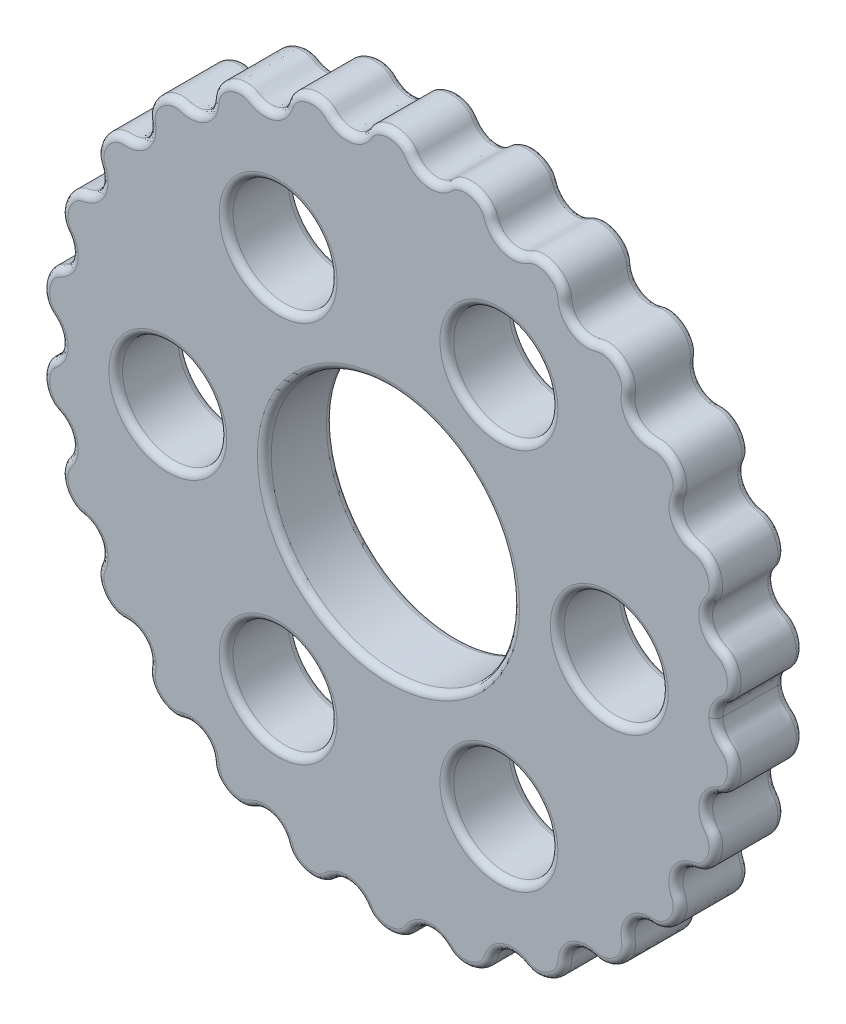
SolidWorks part; units mm, degrees
ref_plane "Front Plane" through (0, 0, 0) normal (0, 0, 1) x (1, 0, 0)
ref_plane "Top Plane" through (0, 0, 0) normal (0, 1, 0) x (1, 0, 0)
ref_plane "Right Plane" through (0, 0, 0) normal (1, 0, 0) x (0, 0, -1)
sketch "Sketch2" plane through (0, 0, 5.6053) normal (0, 0, 1) x (1, 0, 0)
  line L0 (0, 0) -> (16, 0) construction
  circle A1 centre (0, 0) radius 9.0043
  circle A2 centre (8, 13.8564) radius 3.775
  circle A3 centre (16, 0) radius 3.775
  circle A4 centre (8, -13.8564) radius 3.775
  circle A5 centre (-8, -13.8564) radius 3.775
  circle A6 centre (-16, 0) radius 3.775
  circle A7 centre (-8, 13.8564) radius 3.775
  spline S0 degree 4 poles (23.0037, 5.8458) (23.0203, 5.7223) (23.0794, 5.4789) (23.2221, 5.1817) (23.4626, 4.9066) (23.6795, 4.7368) (23.8391, 4.6378) (23.9718, 4.5676) (24.1072, 4.503) (24.2388, 4.4304) (24.4054, 4.3116) (24.5912, 4.1306) (24.7754, 3.876) (24.9327, 3.5431) (25.0483, 3.1257) (25.0761, 2.7055) (25.0224, 2.3013) (24.8965, 1.9437) (24.7582, 1.6923) (24.6064, 1.5045) (24.4596, 1.3769) (24.3107, 1.2527) (24.1813, 1.13) (24.0543, 0.9823) (23.938, 0.8063) (23.8505, 0.6319) (23.7934, 0.4738) (23.7588, 0.3351) (23.7414, 0.2342) (23.7333, 0.1668) (23.7277, 0.0957) (23.725, 0.0326) (23.7245, -0.0144) (23.7273, -0.0932) (23.7343, -0.1857) (23.7483, -0.2803) (23.7722, -0.3912) (23.8037, -0.4996) (23.8526, -0.6319) (23.9324, -0.7986) (24.0371, -0.9605) (24.1664, -1.1132) (24.2951, -1.2379) (24.4038, -1.3312) (24.514, -1.4227) (24.6167, -1.5229) (24.7397, -1.6722) (24.8666, -1.8806) (24.9775, -2.1535) (25.05, -2.49) (25.0678, -2.8386) (25.0298, -3.1905) (24.9348, -3.5366) (24.7807, -3.8663) (24.6006, -4.119) (24.4193, -4.2992) (24.2573, -4.4184) (24.1298, -4.4917) (23.9974, -4.5553) (23.8668, -4.6224) (23.709, -4.7166) (23.4971, -4.8753) (23.2602, -5.13) (23.06, -5.5023) (22.9668, -5.9508) (22.998, -6.362) (23.0998, -6.6748) (23.2181, -6.9001) (23.3176, -7.0522) (23.4035, -7.1692) (23.488, -7.2875) (23.56, -7.4139) (23.6371, -7.5903) (23.7025, -7.8212) (23.7475, -8.1895) (23.7046, -8.6153) (23.5731, -9.0303) (23.3553, -9.414) (23.1236, -9.6966) (22.8856, -9.8973) (22.6643, -10.0268) (22.4772, -10.1012) (22.3354, -10.14) (22.1917, -10.1697) (22.0491, -10.2047) (21.874, -10.26) (21.6255, -10.3685) (21.3269, -10.5711) (21.0437, -10.9023) (20.8569, -11.3338) (20.8056, -11.7447) (20.841, -12.0653) (20.9071, -12.3034) (20.9676, -12.4656) (21.021, -12.5933) (21.0822, -12.7553) (21.1313, -12.9726) (21.1455, -13.2444) (21.0948, -13.6461) (20.9479, -14.051) (20.716, -14.4248) (20.4051, -14.7469) (20.103, -14.9665) (19.8146, -15.1019) (19.5606, -15.1696) (19.3547, -15.1903) (19.2221, -15.1888) (19.1086, -15.1855) (18.995, -15.1853) (18.8815, -15.1895) (18.7118, -15.2065) (18.4439, -15.2645) (18.1117, -15.4058) (17.7742, -15.6727) (17.5121, -16.0483) (17.3806, -16.4277) (17.3468, -16.7368) (17.3574, -16.9752) (17.3781, -17.1416) (17.3988, -17.2742) (17.4171, -17.4411) (17.4116, -17.6602) (17.3598, -17.9256) (17.2132, -18.3039) (16.9296, -18.7242) (16.5497, -19.061) (16.1013, -19.2909) (15.7127, -19.392) (15.4438, -19.4132) (15.2236, -19.3942) (15.0228, -19.3476) (14.8253, -19.2892) (14.5504, -19.237) (14.1962, -19.2348) (13.7976, -19.3265) (13.3929, -19.5509) (13.0927, -19.8602) (12.9191, -20.1735) (12.8336, -20.4318) (12.7947, -20.6157) (12.7743, -20.7647) (12.7615, -20.9144) (12.7433, -21.0637) (12.6954, -21.2634) (12.5957, -21.5045) (12.4256, -21.7711) (12.1716, -22.0409) (11.8129, -22.3094) (11.4108, -22.4937) (10.9862, -22.5887) (10.6101, -22.5864) (10.3721, -22.5473) (10.1892, -22.4907) (10.0584, -22.4347) (9.9338, -22.3664) (9.81, -22.2969) (9.6507, -22.2183) (9.4189, -22.1297) (9.1053, -22.0658) (8.7004, -22.0785) (8.2681, -22.2156) (7.9185, -22.4522) (7.6878, -22.7163) (7.5514, -22.9457) (7.4743, -23.1141) (7.4217, -23.2525) (7.3745, -23.3928) (7.3187, -23.5301) (7.2216, -23.708) (7.0655, -23.913) (6.8362, -24.1258) (6.5262, -24.3219) (6.1144, -24.4927) (5.6801, -24.5722) (5.2446, -24.5597) (4.8794, -24.4637) (4.6581, -24.366) (4.4951, -24.2648) (4.3828, -24.1775) (4.2789, -24.0806) (4.1747, -23.9841) (4.0379, -23.8707) (3.8273, -23.7279) (3.5241, -23.5902) (3.1183, -23.5153) (2.6658, -23.5604) (2.2792, -23.7158) (2.0049, -23.916) (1.8238, -24.1052) (1.71, -24.2525) (1.6267, -24.3758) (1.5466, -24.5011) (1.4565, -24.6199) (1.3207, -24.7622) (1.1279, -24.9136) (0.8712, -25.0555) (0.5491, -25.1669) (0.1207, -25.2418) (-0.3205, -25.2256) (-0.7535, -25.1153) (-1.1028, -24.9304) (-1.3027, -24.7782) (-1.4408, -24.6375) (-1.53, -24.5249) (-1.6084, -24.4048) (-1.6871, -24.2851) (-1.794, -24.141) (-1.9709, -23.9454) (-2.248, -23.731) (-2.6436, -23.5634) (-3.111, -23.5139) (-3.5241, -23.5902) (-3.8273, -23.7279) (-4.0379, -23.8707) (-4.1747, -23.9841) (-4.2789, -24.0806) (-4.3828, -24.1775) (-4.4951, -24.2648) (-4.6581, -24.366) (-4.8794, -24.4637) (-5.2446, -24.5597) (-5.6801, -24.5722) (-6.1144, -24.4927) (-6.5262, -24.3219) (-6.8362, -24.1258) (-7.0655, -23.913) (-7.2216, -23.708) (-7.3187, -23.5301) (-7.3745, -23.3928) (-7.4217, -23.2525) (-7.4743, -23.1141) (-7.5514, -22.9457) (-7.6878, -22.7163) (-7.9185, -22.4522) (-8.2681, -22.2156) (-8.7004, -22.0785) (-9.1053, -22.0658) (-9.4189, -22.1297) (-9.6507, -22.2183) (-9.81, -22.2969) (-9.9338, -22.3664) (-10.0584, -22.4347) (-10.1892, -22.4907) (-10.3721, -22.5473) (-10.6101, -22.5864) (-10.9862, -22.5887) (-11.4108, -22.4937) (-11.8129, -22.3094) (-12.1716, -22.0409) (-12.4256, -21.7711) (-12.5957, -21.5045) (-12.6954, -21.2634) (-12.7433, -21.0637) (-12.7615, -20.9144) (-12.7743, -20.7647) (-12.7947, -20.6157) (-12.8336, -20.4318) (-12.9191, -20.1735) (-13.0927, -19.8602) (-13.3929, -19.5509) (-13.7976, -19.3265) (-14.1962, -19.2348) (-14.5504, -19.237) (-14.8253, -19.2892) (-15.0228, -19.3476) (-15.2236, -19.3942) (-15.4438, -19.4132) (-15.7127, -19.392) (-16.1013, -19.2909) (-16.5497, -19.061) (-16.9296, -18.7242) (-17.2132, -18.3039) (-17.3598, -17.9256) (-17.4116, -17.6602) (-17.4171, -17.4411) (-17.3988, -17.2742) (-17.3781, -17.1416) (-17.3574, -16.9752) (-17.3468, -16.7368) (-17.3806, -16.4277) (-17.5121, -16.0483) (-17.7742, -15.6727) (-18.1117, -15.4058) (-18.4439, -15.2645) (-18.7118, -15.2065) (-18.8815, -15.1895) (-18.995, -15.1853) (-19.1086, -15.1855) (-19.2221, -15.1888) (-19.3547, -15.1903) (-19.5606, -15.1696) (-19.8146, -15.1019) (-20.103, -14.9665) (-20.4051, -14.7469) (-20.716, -14.4248) (-20.9479, -14.051) (-21.0948, -13.6461) (-21.1455, -13.2444) (-21.1313, -12.9726) (-21.0822, -12.7553) (-21.021, -12.5933) (-20.9676, -12.4656) (-20.9071, -12.3034) (-20.841, -12.0653) (-20.8056, -11.7447) (-20.8569, -11.3338) (-21.0437, -10.9023) (-21.3269, -10.5711) (-21.6255, -10.3685) (-21.874, -10.26) (-22.0491, -10.2047) (-22.1917, -10.1697) (-22.3354, -10.14) (-22.4772, -10.1012) (-22.6643, -10.0268) (-22.8856, -9.8973) (-23.1236, -9.6966) (-23.3553, -9.414) (-23.5731, -9.0303) (-23.7046, -8.6153) (-23.7475, -8.1895) (-23.7025, -7.8212) (-23.6371, -7.5903) (-23.56, -7.4139) (-23.488, -7.2875) (-23.4035, -7.1692) (-23.3176, -7.0522) (-23.2181, -6.9001) (-23.0998, -6.6748) (-22.998, -6.362) (-22.9668, -5.9508) (-23.06, -5.5023) (-23.2602, -5.13) (-23.4971, -4.8753) (-23.709, -4.7166) (-23.8668, -4.6224) (-23.9974, -4.5553) (-24.1298, -4.4917) (-24.2573, -4.4184) (-24.4193, -4.2992) (-24.6006, -4.119) (-24.7807, -3.8663) (-24.9348, -3.5366) (-25.0298, -3.1905) (-25.0678, -2.8386) (-25.05, -2.49) (-24.9775, -2.1535) (-24.8666, -1.8806) (-24.7397, -1.6722) (-24.6167, -1.5229) (-24.514, -1.4227) (-24.4038, -1.3312) (-24.2951, -1.2379) (-24.1664, -1.1132) (-24.0371, -0.9605) (-23.9324, -0.7986) (-23.8526, -0.6319) (-23.8037, -0.4996) (-23.7722, -0.3912) (-23.7483, -0.2803) (-23.7343, -0.1857) (-23.7273, -0.0932) (-23.7245, -0.0144) (-23.725, 0.0326) (-23.7277, 0.0957) (-23.7333, 0.1668) (-23.7414, 0.2342) (-23.7588, 0.3351) (-23.7934, 0.4738) (-23.8505, 0.6319) (-23.938, 0.8063) (-24.0543, 0.9823) (-24.1813, 1.13) (-24.3107, 1.2527) (-24.4596, 1.3769) (-24.6064, 1.5045) (-24.7582, 1.6923) (-24.8965, 1.9437) (-25.0224, 2.3014) (-25.0767, 2.7104) (-25.047, 3.1407) (-24.9235, 3.5716) (-24.7509, 3.9196) (-24.5491, 4.1808) (-24.3464, 4.3608) (-24.1669, 4.4726) (-24.0469, 4.5314) (-23.9443, 4.5823) (-23.8099, 4.6547) (-23.6481, 4.7565) (-23.428, 4.9381) (-23.1927, 5.2368) (-23.0695, 5.5154) (-23.0186, 5.7347) (-23.0037, 5.8458) knots 0 0 0 0 0 0.004792 0.009584 0.01247 0.013912 0.015355 0.016798 0.018241 0.019684 0.021127 0.024649 0.02817 0.031692 0.035214 0.041226 0.044232 0.047238 0.049726 0.052214 0.053458 0.054702 0.057189 0.059059 0.060929 0.062799 0.064669 0.065525 0.066381 0.066809 0.067237 0.068093 0.068635 0.069177 0.070262 0.071346 0.072431 0.073516 0.0746 0.076769 0.079523 0.080901 0.082278 0.083655 0.085032 0.086409 0.087786 0.091081 0.094376 0.097671 0.100966 0.104448 0.10793 0.111412 0.114894 0.116306 0.117718 0.119129 0.120541 0.121953 0.123365 0.126188 0.130698 0.135209 0.139389 0.143569 0.146362 0.147758 0.149154 0.150551 0.151947 0.153343 0.154739 0.15794 0.16114 0.167541 0.171036 0.174532 0.178027 0.181523 0.182934 0.184345 0.185756 0.187168 0.188579 0.18999 0.192812 0.197567 0.202321 0.20648 0.21064 0.213301 0.214632 0.215963 0.217294 0.218625 0.221287 0.224494 0.227701 0.234115 0.237687 0.241259 0.244831 0.248403 0.249859 0.251314 0.25277 0.253498 0.254226 0.255682 0.257137 0.260049 0.264737 0.269426 0.273427 0.277429 0.280009 0.281299 0.282589 0.283879 0.285169 0.287749 0.290984 0.294219 0.30069 0.307051 0.310231 0.313411 0.316051 0.317371 0.318692 0.321332 0.323972 0.328095 0.332218 0.336872 0.341526 0.344415 0.34586 0.347305 0.348749 0.350194 0.351639 0.353084 0.356629 0.360174 0.363719 0.367265 0.373774 0.377029 0.380283 0.381649 0.383014 0.384379 0.385745 0.38711 0.388475 0.391206 0.395267 0.399327 0.403873 0.408418 0.411264 0.412687 0.41411 0.415533 0.416956 0.418379 0.419802 0.423312 0.426821 0.43033 0.433839 0.440376 0.443644 0.446913 0.448278 0.449644 0.451009 0.452374 0.45374 0.455105 0.457836 0.462139 0.466442 0.470768 0.475094 0.477954 0.479385 0.480815 0.482245 0.483675 0.485106 0.486536 0.489798 0.493061 0.496324 0.499586 0.506451 0.509883 0.513315 0.514694 0.516072 0.51745 0.518829 0.520207 0.521585 0.524342 0.52895 0.533558 0.537861 0.542164 0.544895 0.54626 0.547626 0.548991 0.550356 0.551722 0.553087 0.556356 0.559624 0.566161 0.56967 0.573179 0.576689 0.580198 0.581621 0.583044 0.584467 0.58589 0.587313 0.588736 0.591582 0.596127 0.600673 0.604734 0.608794 0.611525 0.61289 0.614256 0.615621 0.616986 0.618351 0.619717 0.622971 0.626226 0.632735 0.636281 0.639826 0.643371 0.646916 0.648361 0.649806 0.651251 0.652695 0.65414 0.655585 0.658475 0.663128 0.667782 0.671905 0.676028 0.678668 0.681309 0.682629 0.683949 0.686589 0.689769 0.692949 0.69931 0.705781 0.709016 0.712252 0.714831 0.716121 0.717411 0.718701 0.719991 0.722571 0.726573 0.730574 0.735263 0.739951 0.742863 0.744318 0.745774 0.746502 0.74723 0.748686 0.750142 0.751597 0.755169 0.758741 0.762313 0.765885 0.772299 0.775506 0.778713 0.781375 0.782706 0.784037 0.785368 0.786699 0.78936 0.79352 0.797679 0.802433 0.807188 0.81001 0.811421 0.812832 0.814244 0.815655 0.817066 0.818477 0.821973 0.825468 0.828964 0.832459 0.83886 0.84206 0.845261 0.846657 0.848053 0.84945 0.850846 0.852242 0.853638 0.856431 0.860611 0.864792 0.869302 0.873812 0.876635 0.878047 0.879459 0.880871 0.882282 0.883694 0.885106 0.888588 0.89207 0.895552 0.899034 0.902329 0.905624 0.908919 0.912214 0.913591 0.914968 0.916345 0.917722 0.919099 0.920477 0.923231 0.9254 0.926485 0.927569 0.928654 0.929738 0.930823 0.931365 0.931907 0.932763 0.933191 0.933619 0.934475 0.935331 0.937201 0.939071 0.940941 0.942811 0.945298 0.946542 0.947786 0.950274 0.952762 0.955768 0.958774 0.964786 0.968499 0.972211 0.975924 0.979636 0.981104 0.982571 0.984039 0.984773 0.985507 0.988442 0.991378 0.995689 1 1 1 1 1 construction
  spline S1 degree 4 poles (23.725, 0) (23.725, -0.0122) (23.7253, -0.0367) (23.7273, -0.0932) (23.7343, -0.1857) (23.7483, -0.2803) (23.7722, -0.3912) (23.8037, -0.4996) (23.8526, -0.6319) (23.9324, -0.7986) (24.0371, -0.9605) (24.1664, -1.1132) (24.2951, -1.2379) (24.4038, -1.3312) (24.514, -1.4227) (24.6167, -1.5229) (24.7397, -1.6722) (24.8666, -1.8806) (24.9775, -2.1535) (25.05, -2.49) (25.0678, -2.8386) (25.0298, -3.1905) (24.9348, -3.5366) (24.7807, -3.8663) (24.6006, -4.119) (24.4193, -4.2992) (24.2573, -4.4184) (24.1298, -4.4917) (23.9974, -4.5553) (23.8668, -4.6224) (23.709, -4.7166) (23.4971, -4.8753) (23.2602, -5.13) (23.06, -5.5023) (22.9668, -5.9508) (22.998, -6.362) (23.0998, -6.6748) (23.2181, -6.9001) (23.3176, -7.0522) (23.4035, -7.1692) (23.488, -7.2875) (23.56, -7.4139) (23.6371, -7.5903) (23.7025, -7.8212) (23.7475, -8.1895) (23.7046, -8.6153) (23.5731, -9.0303) (23.3553, -9.414) (23.1236, -9.6966) (22.8856, -9.8973) (22.6643, -10.0268) (22.4772, -10.1012) (22.3354, -10.14) (22.1917, -10.1697) (22.0491, -10.2047) (21.874, -10.26) (21.6255, -10.3685) (21.3269, -10.5711) (21.0437, -10.9023) (20.8569, -11.3338) (20.8056, -11.7447) (20.841, -12.0653) (20.9071, -12.3034) (20.9676, -12.4656) (21.021, -12.5933) (21.0822, -12.7553) (21.1313, -12.9726) (21.1455, -13.2444) (21.0948, -13.6461) (20.9479, -14.051) (20.716, -14.4248) (20.4051, -14.7469) (20.103, -14.9665) (19.8146, -15.1019) (19.5606, -15.1696) (19.3547, -15.1903) (19.2221, -15.1888) (19.1086, -15.1855) (18.995, -15.1853) (18.8815, -15.1895) (18.7118, -15.2065) (18.4439, -15.2645) (18.1117, -15.4058) (17.7742, -15.6727) (17.5121, -16.0483) (17.3806, -16.4277) (17.3468, -16.7368) (17.3574, -16.9752) (17.3781, -17.1416) (17.3988, -17.2742) (17.4171, -17.4411) (17.4116, -17.6602) (17.3598, -17.9256) (17.2132, -18.3039) (16.9296, -18.7242) (16.5497, -19.061) (16.1013, -19.2909) (15.7127, -19.392) (15.4438, -19.4132) (15.2236, -19.3942) (15.0228, -19.3476) (14.8253, -19.2892) (14.5504, -19.237) (14.1962, -19.2348) (13.7976, -19.3265) (13.3929, -19.5509) (13.0927, -19.8602) (12.9191, -20.1735) (12.8336, -20.4318) (12.7947, -20.6157) (12.7743, -20.7647) (12.7615, -20.9144) (12.7433, -21.0637) (12.6954, -21.2634) (12.5957, -21.5045) (12.4256, -21.7711) (12.1716, -22.0409) (11.8129, -22.3094) (11.4108, -22.4937) (10.9862, -22.5887) (10.6101, -22.5864) (10.3721, -22.5473) (10.1892, -22.4907) (10.0584, -22.4347) (9.9338, -22.3664) (9.81, -22.2969) (9.6507, -22.2183) (9.4189, -22.1297) (9.1053, -22.0658) (8.7004, -22.0785) (8.2681, -22.2156) (7.9185, -22.4522) (7.6878, -22.7163) (7.5514, -22.9457) (7.4743, -23.1141) (7.4217, -23.2525) (7.3745, -23.3928) (7.3187, -23.5301) (7.2216, -23.708) (7.0655, -23.913) (6.8362, -24.1258) (6.5262, -24.3219) (6.1144, -24.4927) (5.6801, -24.5722) (5.2446, -24.5597) (4.8794, -24.4637) (4.6581, -24.366) (4.4951, -24.2648) (4.3828, -24.1775) (4.2789, -24.0806) (4.1747, -23.9841) (4.0379, -23.8707) (3.8273, -23.7279) (3.5241, -23.5902) (3.1183, -23.5153) (2.6658, -23.5604) (2.2792, -23.7158) (2.0049, -23.916) (1.8238, -24.1052) (1.71, -24.2525) (1.6267, -24.3758) (1.5466, -24.5011) (1.4565, -24.6199) (1.3207, -24.7622) (1.1279, -24.9136) (0.8712, -25.0555) (0.5491, -25.1669) (0.1207, -25.2418) (-0.3205, -25.2256) (-0.7535, -25.1153) (-1.1028, -24.9304) (-1.3027, -24.7782) (-1.4408, -24.6375) (-1.53, -24.5249) (-1.6084, -24.4048) (-1.6871, -24.2851) (-1.794, -24.141) (-1.9709, -23.9454) (-2.248, -23.731) (-2.6436, -23.5634) (-3.111, -23.5139) (-3.5241, -23.5902) (-3.8273, -23.7279) (-4.0379, -23.8707) (-4.1747, -23.9841) (-4.2789, -24.0806) (-4.3828, -24.1775) (-4.4951, -24.2648) (-4.6581, -24.366) (-4.8794, -24.4637) (-5.2446, -24.5597) (-5.6801, -24.5722) (-6.1144, -24.4927) (-6.5262, -24.3219) (-6.8362, -24.1258) (-7.0655, -23.913) (-7.2216, -23.708) (-7.3187, -23.5301) (-7.3745, -23.3928) (-7.4217, -23.2525) (-7.4743, -23.1141) (-7.5514, -22.9457) (-7.6878, -22.7163) (-7.9185, -22.4522) (-8.2681, -22.2156) (-8.7004, -22.0785) (-9.1053, -22.0658) (-9.4189, -22.1297) (-9.6507, -22.2183) (-9.81, -22.2969) (-9.9338, -22.3664) (-10.0584, -22.4347) (-10.1892, -22.4907) (-10.3721, -22.5473) (-10.6101, -22.5864) (-10.9862, -22.5887) (-11.4108, -22.4937) (-11.8129, -22.3094) (-12.1716, -22.0409) (-12.4256, -21.7711) (-12.5957, -21.5045) (-12.6954, -21.2634) (-12.7433, -21.0637) (-12.7615, -20.9144) (-12.7743, -20.7647) (-12.7947, -20.6157) (-12.8336, -20.4318) (-12.9191, -20.1735) (-13.0927, -19.8602) (-13.3929, -19.5509) (-13.7976, -19.3265) (-14.1962, -19.2348) (-14.5504, -19.237) (-14.8253, -19.2892) (-15.0228, -19.3476) (-15.2236, -19.3942) (-15.4438, -19.4132) (-15.7127, -19.392) (-16.1013, -19.2909) (-16.5497, -19.061) (-16.9296, -18.7242) (-17.2132, -18.3039) (-17.3598, -17.9256) (-17.4116, -17.6602) (-17.4171, -17.4411) (-17.3988, -17.2742) (-17.3781, -17.1416) (-17.3574, -16.9752) (-17.3468, -16.7368) (-17.3806, -16.4277) (-17.5121, -16.0483) (-17.7742, -15.6727) (-18.1117, -15.4058) (-18.4439, -15.2645) (-18.7118, -15.2065) (-18.8815, -15.1895) (-18.995, -15.1853) (-19.1086, -15.1855) (-19.2221, -15.1888) (-19.3547, -15.1903) (-19.5606, -15.1696) (-19.8146, -15.1019) (-20.103, -14.9665) (-20.4051, -14.7469) (-20.716, -14.4248) (-20.9479, -14.051) (-21.0948, -13.6461) (-21.1455, -13.2444) (-21.1313, -12.9726) (-21.0822, -12.7553) (-21.021, -12.5933) (-20.9676, -12.4656) (-20.9071, -12.3034) (-20.841, -12.0653) (-20.8056, -11.7447) (-20.8569, -11.3338) (-21.0437, -10.9023) (-21.3269, -10.5711) (-21.6255, -10.3685) (-21.874, -10.26) (-22.0491, -10.2047) (-22.1917, -10.1697) (-22.3354, -10.14) (-22.4772, -10.1012) (-22.6643, -10.0268) (-22.8856, -9.8973) (-23.1236, -9.6966) (-23.3553, -9.414) (-23.5731, -9.0303) (-23.7046, -8.6153) (-23.7475, -8.1895) (-23.7025, -7.8212) (-23.6371, -7.5903) (-23.56, -7.4139) (-23.488, -7.2875) (-23.4035, -7.1692) (-23.3176, -7.0522) (-23.2181, -6.9001) (-23.0998, -6.6748) (-22.998, -6.362) (-22.9668, -5.9508) (-23.06, -5.5023) (-23.2602, -5.13) (-23.4971, -4.8753) (-23.709, -4.7166) (-23.8668, -4.6224) (-23.9974, -4.5553) (-24.1298, -4.4917) (-24.2573, -4.4184) (-24.4193, -4.2992) (-24.6006, -4.119) (-24.7807, -3.8663) (-24.9348, -3.5366) (-25.0298, -3.1905) (-25.0678, -2.8386) (-25.05, -2.49) (-24.9775, -2.1535) (-24.8666, -1.8806) (-24.7397, -1.6722) (-24.6167, -1.5229) (-24.514, -1.4227) (-24.4038, -1.3312) (-24.2951, -1.2379) (-24.1664, -1.1132) (-24.0371, -0.9605) (-23.9324, -0.7986) (-23.8526, -0.6319) (-23.8037, -0.4996) (-23.7722, -0.3912) (-23.7483, -0.2803) (-23.7343, -0.1857) (-23.7273, -0.0932) (-23.7253, -0.0367) (-23.725, -0.0122) (-23.725, 0) knots 0.068093 0.068093 0.068093 0.068093 0.068093 0.068635 0.069177 0.070262 0.071346 0.072431 0.073516 0.0746 0.076769 0.079523 0.080901 0.082278 0.083655 0.085032 0.086409 0.087786 0.091081 0.094376 0.097671 0.100966 0.104448 0.10793 0.111412 0.114894 0.116306 0.117718 0.119129 0.120541 0.121953 0.123365 0.126188 0.130698 0.135209 0.139389 0.143569 0.146362 0.147758 0.149154 0.150551 0.151947 0.153343 0.154739 0.15794 0.16114 0.167541 0.171036 0.174532 0.178027 0.181523 0.182934 0.184345 0.185756 0.187168 0.188579 0.18999 0.192812 0.197567 0.202321 0.20648 0.21064 0.213301 0.214632 0.215963 0.217294 0.218625 0.221287 0.224494 0.227701 0.234115 0.237687 0.241259 0.244831 0.248403 0.249859 0.251314 0.25277 0.253498 0.254226 0.255682 0.257137 0.260049 0.264737 0.269426 0.273427 0.277429 0.280009 0.281299 0.282589 0.283879 0.285169 0.287749 0.290984 0.294219 0.30069 0.307051 0.310231 0.313411 0.316051 0.317371 0.318692 0.321332 0.323972 0.328095 0.332218 0.336872 0.341526 0.344415 0.34586 0.347305 0.348749 0.350194 0.351639 0.353084 0.356629 0.360174 0.363719 0.367265 0.373774 0.377029 0.380283 0.381649 0.383014 0.384379 0.385745 0.38711 0.388475 0.391206 0.395267 0.399327 0.403873 0.408418 0.411264 0.412687 0.41411 0.415533 0.416956 0.418379 0.419802 0.423312 0.426821 0.43033 0.433839 0.440376 0.443644 0.446913 0.448278 0.449644 0.451009 0.452374 0.45374 0.455105 0.457836 0.462139 0.466442 0.470768 0.475094 0.477954 0.479385 0.480815 0.482245 0.483675 0.485106 0.486536 0.489798 0.493061 0.496324 0.499586 0.506451 0.509883 0.513315 0.514694 0.516072 0.51745 0.518829 0.520207 0.521585 0.524342 0.52895 0.533558 0.537861 0.542164 0.544895 0.54626 0.547626 0.548991 0.550356 0.551722 0.553087 0.556356 0.559624 0.566161 0.56967 0.573179 0.576689 0.580198 0.581621 0.583044 0.584467 0.58589 0.587313 0.588736 0.591582 0.596127 0.600673 0.604734 0.608794 0.611525 0.61289 0.614256 0.615621 0.616986 0.618351 0.619717 0.622971 0.626226 0.632735 0.636281 0.639826 0.643371 0.646916 0.648361 0.649806 0.651251 0.652695 0.65414 0.655585 0.658475 0.663128 0.667782 0.671905 0.676028 0.678668 0.681309 0.682629 0.683949 0.686589 0.689769 0.692949 0.69931 0.705781 0.709016 0.712252 0.714831 0.716121 0.717411 0.718701 0.719991 0.722571 0.726573 0.730574 0.735263 0.739951 0.742863 0.744318 0.745774 0.746502 0.74723 0.748686 0.750142 0.751597 0.755169 0.758741 0.762313 0.765885 0.772299 0.775506 0.778713 0.781375 0.782706 0.784037 0.785368 0.786699 0.78936 0.79352 0.797679 0.802433 0.807188 0.81001 0.811421 0.812832 0.814244 0.815655 0.817066 0.818477 0.821973 0.825468 0.828964 0.832459 0.83886 0.84206 0.845261 0.846657 0.848053 0.84945 0.850846 0.852242 0.853638 0.856431 0.860611 0.864792 0.869302 0.873812 0.876635 0.878047 0.879459 0.880871 0.882282 0.883694 0.885106 0.888588 0.89207 0.895552 0.899034 0.902329 0.905624 0.908919 0.912214 0.913591 0.914968 0.916345 0.917722 0.919099 0.920477 0.923231 0.9254 0.926485 0.927569 0.928654 0.929738 0.930823 0.931365 0.931907 0.931907 0.931907 0.931907 0.931907
  spline S2 degree 4 poles (23.725, 0) (23.725, 0.0122) (23.7253, 0.0367) (23.7273, 0.0932) (23.7343, 0.1857) (23.7483, 0.2803) (23.7722, 0.3912) (23.8037, 0.4996) (23.8526, 0.6319) (23.9324, 0.7986) (24.0371, 0.9605) (24.1664, 1.1132) (24.2951, 1.2379) (24.4038, 1.3312) (24.514, 1.4227) (24.6167, 1.5229) (24.7397, 1.6722) (24.8666, 1.8806) (24.9775, 2.1535) (25.05, 2.49) (25.0678, 2.8386) (25.0298, 3.1905) (24.9348, 3.5366) (24.7807, 3.8663) (24.6006, 4.119) (24.4193, 4.2992) (24.2573, 4.4184) (24.1298, 4.4917) (23.9974, 4.5553) (23.8668, 4.6224) (23.709, 4.7166) (23.4971, 4.8753) (23.2602, 5.13) (23.06, 5.5023) (22.9668, 5.9508) (22.998, 6.362) (23.0998, 6.6748) (23.2181, 6.9001) (23.3176, 7.0522) (23.4035, 7.1692) (23.488, 7.2875) (23.56, 7.4139) (23.6371, 7.5903) (23.7025, 7.8212) (23.7475, 8.1895) (23.7046, 8.6153) (23.5731, 9.0303) (23.3553, 9.414) (23.1236, 9.6966) (22.8856, 9.8973) (22.6643, 10.0268) (22.4772, 10.1012) (22.3354, 10.14) (22.1917, 10.1697) (22.0491, 10.2047) (21.874, 10.26) (21.6255, 10.3685) (21.3269, 10.5711) (21.0437, 10.9023) (20.8569, 11.3338) (20.8056, 11.7447) (20.841, 12.0653) (20.9071, 12.3034) (20.9676, 12.4656) (21.021, 12.5933) (21.0822, 12.7553) (21.1313, 12.9726) (21.1455, 13.2444) (21.0948, 13.6461) (20.9479, 14.051) (20.716, 14.4248) (20.4051, 14.7469) (20.103, 14.9665) (19.8146, 15.1019) (19.5606, 15.1696) (19.3547, 15.1903) (19.2221, 15.1888) (19.1086, 15.1855) (18.995, 15.1853) (18.8815, 15.1895) (18.7118, 15.2065) (18.4439, 15.2645) (18.1117, 15.4058) (17.7742, 15.6727) (17.5121, 16.0483) (17.3806, 16.4277) (17.3468, 16.7368) (17.3574, 16.9752) (17.3781, 17.1416) (17.3988, 17.2742) (17.4171, 17.4411) (17.4116, 17.6602) (17.3598, 17.9256) (17.2132, 18.3039) (16.9296, 18.7242) (16.5497, 19.061) (16.1013, 19.2909) (15.7127, 19.392) (15.4438, 19.4132) (15.2236, 19.3942) (15.0228, 19.3476) (14.8253, 19.2892) (14.5504, 19.237) (14.1962, 19.2348) (13.7976, 19.3265) (13.3929, 19.5509) (13.0927, 19.8602) (12.9191, 20.1735) (12.8336, 20.4318) (12.7947, 20.6157) (12.7743, 20.7647) (12.7615, 20.9144) (12.7433, 21.0637) (12.6954, 21.2634) (12.5957, 21.5045) (12.4256, 21.7711) (12.1716, 22.0409) (11.8129, 22.3094) (11.4108, 22.4937) (10.9862, 22.5887) (10.6101, 22.5864) (10.3721, 22.5473) (10.1892, 22.4907) (10.0584, 22.4347) (9.9338, 22.3664) (9.81, 22.2969) (9.6507, 22.2183) (9.4189, 22.1297) (9.1053, 22.0658) (8.7004, 22.0785) (8.2681, 22.2156) (7.9185, 22.4522) (7.6878, 22.7163) (7.5514, 22.9457) (7.4743, 23.1141) (7.4217, 23.2525) (7.3745, 23.3928) (7.3187, 23.5301) (7.2216, 23.708) (7.0655, 23.913) (6.8362, 24.1258) (6.5262, 24.3219) (6.1144, 24.4927) (5.6801, 24.5722) (5.2446, 24.5597) (4.8794, 24.4637) (4.6581, 24.366) (4.4951, 24.2648) (4.3828, 24.1775) (4.2789, 24.0806) (4.1747, 23.9841) (4.0379, 23.8707) (3.8273, 23.7279) (3.5241, 23.5902) (3.1183, 23.5153) (2.6658, 23.5604) (2.2792, 23.7158) (2.0049, 23.916) (1.8238, 24.1052) (1.71, 24.2525) (1.6267, 24.3758) (1.5466, 24.5011) (1.4565, 24.6199) (1.3207, 24.7622) (1.1279, 24.9136) (0.8712, 25.0555) (0.5491, 25.1669) (0.1207, 25.2418) (-0.3205, 25.2256) (-0.7535, 25.1153) (-1.1028, 24.9304) (-1.3027, 24.7782) (-1.4408, 24.6375) (-1.53, 24.5249) (-1.6084, 24.4048) (-1.6871, 24.2851) (-1.794, 24.141) (-1.9709, 23.9454) (-2.248, 23.731) (-2.6436, 23.5634) (-3.111, 23.5139) (-3.5241, 23.5902) (-3.8273, 23.7279) (-4.0379, 23.8707) (-4.1747, 23.9841) (-4.2789, 24.0806) (-4.3828, 24.1775) (-4.4951, 24.2648) (-4.6581, 24.366) (-4.8794, 24.4637) (-5.2446, 24.5597) (-5.6801, 24.5722) (-6.1144, 24.4927) (-6.5262, 24.3219) (-6.8362, 24.1258) (-7.0655, 23.913) (-7.2216, 23.708) (-7.3187, 23.5301) (-7.3745, 23.3928) (-7.4217, 23.2525) (-7.4743, 23.1141) (-7.5514, 22.9457) (-7.6878, 22.7163) (-7.9185, 22.4522) (-8.2681, 22.2156) (-8.7004, 22.0785) (-9.1053, 22.0658) (-9.4189, 22.1297) (-9.6507, 22.2183) (-9.81, 22.2969) (-9.9338, 22.3664) (-10.0584, 22.4347) (-10.1892, 22.4907) (-10.3721, 22.5473) (-10.6101, 22.5864) (-10.9862, 22.5887) (-11.4108, 22.4937) (-11.8129, 22.3094) (-12.1716, 22.0409) (-12.4256, 21.7711) (-12.5957, 21.5045) (-12.6954, 21.2634) (-12.7433, 21.0637) (-12.7615, 20.9144) (-12.7743, 20.7647) (-12.7947, 20.6157) (-12.8336, 20.4318) (-12.9191, 20.1735) (-13.0927, 19.8602) (-13.3929, 19.5509) (-13.7976, 19.3265) (-14.1962, 19.2348) (-14.5504, 19.237) (-14.8253, 19.2892) (-15.0228, 19.3476) (-15.2236, 19.3942) (-15.4438, 19.4132) (-15.7127, 19.392) (-16.1013, 19.2909) (-16.5497, 19.061) (-16.9296, 18.7242) (-17.2132, 18.3039) (-17.3598, 17.9256) (-17.4116, 17.6602) (-17.4171, 17.4411) (-17.3988, 17.2742) (-17.3781, 17.1416) (-17.3574, 16.9752) (-17.3468, 16.7368) (-17.3806, 16.4277) (-17.5121, 16.0483) (-17.7742, 15.6727) (-18.1117, 15.4058) (-18.4439, 15.2645) (-18.7118, 15.2065) (-18.8815, 15.1895) (-18.995, 15.1853) (-19.1086, 15.1855) (-19.2221, 15.1888) (-19.3547, 15.1903) (-19.5606, 15.1696) (-19.8146, 15.1019) (-20.103, 14.9665) (-20.4051, 14.7469) (-20.716, 14.4248) (-20.9479, 14.051) (-21.0948, 13.6461) (-21.1455, 13.2444) (-21.1313, 12.9726) (-21.0822, 12.7553) (-21.021, 12.5933) (-20.9676, 12.4656) (-20.9071, 12.3034) (-20.841, 12.0653) (-20.8056, 11.7447) (-20.8569, 11.3338) (-21.0437, 10.9023) (-21.3269, 10.5711) (-21.6255, 10.3685) (-21.874, 10.26) (-22.0491, 10.2047) (-22.1917, 10.1697) (-22.3354, 10.14) (-22.4772, 10.1012) (-22.6643, 10.0268) (-22.8856, 9.8973) (-23.1236, 9.6966) (-23.3553, 9.414) (-23.5731, 9.0303) (-23.7046, 8.6153) (-23.7475, 8.1895) (-23.7025, 7.8212) (-23.6371, 7.5903) (-23.56, 7.4139) (-23.488, 7.2875) (-23.4035, 7.1692) (-23.3176, 7.0522) (-23.2181, 6.9001) (-23.0998, 6.6748) (-22.998, 6.362) (-22.9668, 5.9508) (-23.06, 5.5023) (-23.2602, 5.13) (-23.4971, 4.8753) (-23.709, 4.7166) (-23.8668, 4.6224) (-23.9974, 4.5553) (-24.1298, 4.4917) (-24.2573, 4.4184) (-24.4193, 4.2992) (-24.6006, 4.119) (-24.7807, 3.8663) (-24.9348, 3.5366) (-25.0298, 3.1905) (-25.0678, 2.8386) (-25.05, 2.49) (-24.9775, 2.1535) (-24.8666, 1.8806) (-24.7397, 1.6722) (-24.6167, 1.5229) (-24.514, 1.4227) (-24.4038, 1.3312) (-24.2951, 1.2379) (-24.1664, 1.1132) (-24.0371, 0.9605) (-23.9324, 0.7986) (-23.8526, 0.6319) (-23.8037, 0.4996) (-23.7722, 0.3912) (-23.7483, 0.2803) (-23.7343, 0.1857) (-23.7273, 0.0932) (-23.7253, 0.0367) (-23.725, 0.0122) (-23.725, 0) knots 0.068093 0.068093 0.068093 0.068093 0.068093 0.068635 0.069177 0.070262 0.071346 0.072431 0.073516 0.0746 0.076769 0.079523 0.080901 0.082278 0.083655 0.085032 0.086409 0.087786 0.091081 0.094376 0.097671 0.100966 0.104448 0.10793 0.111412 0.114894 0.116306 0.117718 0.119129 0.120541 0.121953 0.123365 0.126188 0.130698 0.135209 0.139389 0.143569 0.146362 0.147758 0.149154 0.150551 0.151947 0.153343 0.154739 0.15794 0.16114 0.167541 0.171036 0.174532 0.178027 0.181523 0.182934 0.184345 0.185756 0.187168 0.188579 0.18999 0.192812 0.197567 0.202321 0.20648 0.21064 0.213301 0.214632 0.215963 0.217294 0.218625 0.221287 0.224494 0.227701 0.234115 0.237687 0.241259 0.244831 0.248403 0.249859 0.251314 0.25277 0.253498 0.254226 0.255682 0.257137 0.260049 0.264737 0.269426 0.273427 0.277429 0.280009 0.281299 0.282589 0.283879 0.285169 0.287749 0.290984 0.294219 0.30069 0.307051 0.310231 0.313411 0.316051 0.317371 0.318692 0.321332 0.323972 0.328095 0.332218 0.336872 0.341526 0.344415 0.34586 0.347305 0.348749 0.350194 0.351639 0.353084 0.356629 0.360174 0.363719 0.367265 0.373774 0.377029 0.380283 0.381649 0.383014 0.384379 0.385745 0.38711 0.388475 0.391206 0.395267 0.399327 0.403873 0.408418 0.411264 0.412687 0.41411 0.415533 0.416956 0.418379 0.419802 0.423312 0.426821 0.43033 0.433839 0.440376 0.443644 0.446913 0.448278 0.449644 0.451009 0.452374 0.45374 0.455105 0.457836 0.462139 0.466442 0.470768 0.475094 0.477954 0.479385 0.480815 0.482245 0.483675 0.485106 0.486536 0.489798 0.493061 0.496324 0.499586 0.506451 0.509883 0.513315 0.514694 0.516072 0.51745 0.518829 0.520207 0.521585 0.524342 0.52895 0.533558 0.537861 0.542164 0.544895 0.54626 0.547626 0.548991 0.550356 0.551722 0.553087 0.556356 0.559624 0.566161 0.56967 0.573179 0.576689 0.580198 0.581621 0.583044 0.584467 0.58589 0.587313 0.588736 0.591582 0.596127 0.600673 0.604734 0.608794 0.611525 0.61289 0.614256 0.615621 0.616986 0.618351 0.619717 0.622971 0.626226 0.632735 0.636281 0.639826 0.643371 0.646916 0.648361 0.649806 0.651251 0.652695 0.65414 0.655585 0.658475 0.663128 0.667782 0.671905 0.676028 0.678668 0.681309 0.682629 0.683949 0.686589 0.689769 0.692949 0.69931 0.705781 0.709016 0.712252 0.714831 0.716121 0.717411 0.718701 0.719991 0.722571 0.726573 0.730574 0.735263 0.739951 0.742863 0.744318 0.745774 0.746502 0.74723 0.748686 0.750142 0.751597 0.755169 0.758741 0.762313 0.765885 0.772299 0.775506 0.778713 0.781375 0.782706 0.784037 0.785368 0.786699 0.78936 0.79352 0.797679 0.802433 0.807188 0.81001 0.811421 0.812832 0.814244 0.815655 0.817066 0.818477 0.821973 0.825468 0.828964 0.832459 0.83886 0.84206 0.845261 0.846657 0.848053 0.84945 0.850846 0.852242 0.853638 0.856431 0.860611 0.864792 0.869302 0.873812 0.876635 0.878047 0.879459 0.880871 0.882282 0.883694 0.885106 0.888588 0.89207 0.895552 0.899034 0.902329 0.905624 0.908919 0.912214 0.913591 0.914968 0.916345 0.917722 0.919099 0.920477 0.923231 0.9254 0.926485 0.927569 0.928654 0.929738 0.930823 0.931365 0.931907 0.931907 0.931907 0.931907 0.931907
  point P22 (0, 0)
  dimension "D1" = 6
extrude "Boss-Extrude1" add sketch "Sketch2" against normal blind 5
fillet "Fillet1" radius 0.5 18 edges at (11.775, 13.8564, 0.6053) (-4.225, 13.8564, 0.6053) (9.0043, 0, 0.6053) (19.775, 0, 0.6053) (-12.225, 0, 0.6053) (-4.225, -13.8564, 0.6053) (11.775, -13.8564, 0.6053) (11.775, -13.8564, 5.6053) (-4.225, -13.8564, 5.6053) (9.0043, 0, 5.6053) (-12.225, 0, 5.6053) (-4.225, 13.8564, 5.6053) (11.775, 13.8564, 5.6053) (19.775, 0, 5.6053)
